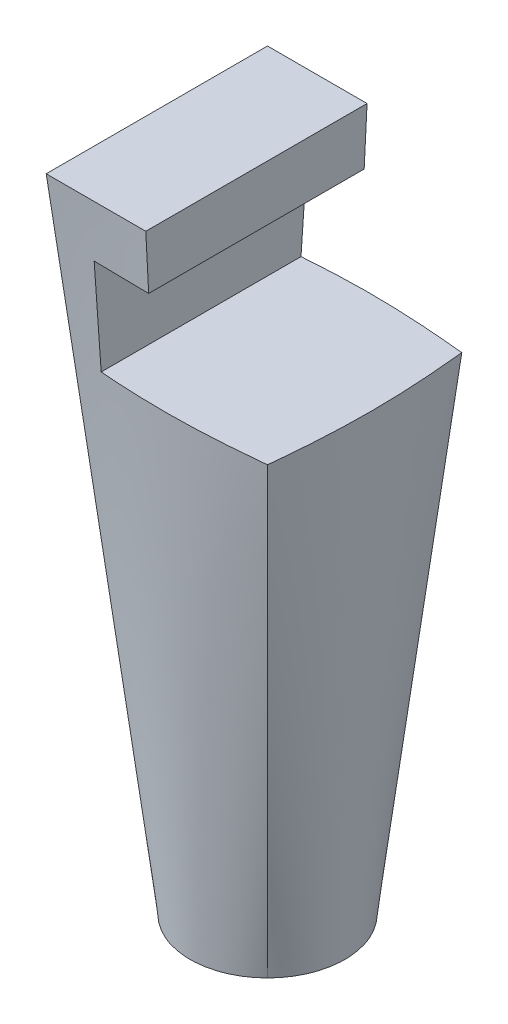
SolidWorks part; units mm, degrees
ref_plane "Front Plane" through (0, 0, 0) normal (0, 0, 1) x (1, 0, 0)
ref_plane "Top Plane" through (0, 0, 0) normal (0, 1, 0) x (1, 0, 0)
ref_plane "Right Plane" through (0, 0, 0) normal (1, 0, 0) x (0, 0, -1)
ref_plane "Plane1" through (0, 14.5, 0) normal (0, 1, 0) x (1, 0, 0)
sketch "Sketch1" plane through (0, 14.5, 0) normal (0, 1, 0) x (1, 0, 0)
  line L1 (-2.5, -2.5) -> (2.5, -2.5)
  line L2 (-2.5, -2.5) -> (-2.5, 2.5)
  line L3 (-2.5, 2.5) -> (2.5, 2.5)
  line L4 (2.5, -2.5) -> (2.5, 2.5)
  point P5 (0, -2.5)
  point P7 (-2.5, 0)
  dimension "D1" = 5
  dimension "D2" = 5
sketch "Sketch4" plane through (0, 0, 0) normal (0, 1, 0) x (1, 0, 0)
  circle A0 centre (0, 0) radius 1.75
  dimension "D1" = 3.5
loft "Loft1" add profiles "Sketch4", "Sketch1"
sketch "Sketch8" plane through (0, 0, 0) normal (0, 0, 1) x (1, 0, 0)
  line L0 (0, 0) -> (2.1952, 11)
  line L1 (-1.5, 13.25) -> (-0.25, 13.25)
  line L2 (-1.5, 13.25) -> (-1.5, 11)
  line L3 (-1.5, 11) -> (3.1518, 11)
  line L5 (-0.25, 13.25) -> (-0.25, 14.7729)
  line L6 (1.2374, 0) -> (2.5, 14.5) construction
  line L7 (-1.2374, 0) -> (1.2374, 0) construction
  line L8 (-0.25, 14.7729) -> (3.1518, 14.7729)
  line L9 (3.1518, 14.7729) -> (3.1518, 11)
  dimension "D1" = 11
  dimension "D2" = 2.25
  dimension "D3" = 1.5
  dimension "D4" = 1.25
extrude "Cut-Extrude3" cut sketch "Sketch8" against normal blind 10 and the other way blind 10 contours L1 L2 L3 region at (1.0328, 12.7496, 0)
sketch "Sketch3" plane through (0, 0, 0) normal (0, -1, 0) x (1, 0, 0)
  circle A0 centre (0, 0) radius 1
  dimension "D1" = 2
extrude "Cut-Extrude2" cut sketch "Sketch3" against normal blind 8 contours A0
chamfer "Chamfer1" distance 1 angle 45 1 edges at (0, 8, -1)
